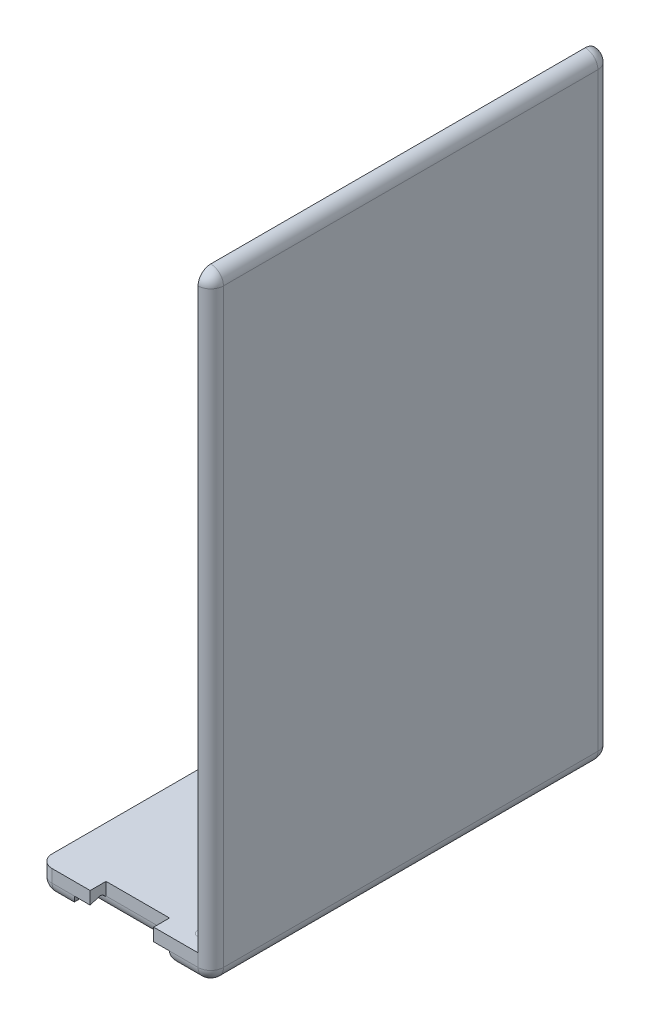
SolidWorks part; units mm, degrees
note: The reader was unsure of these and kept them because the rebuilt part matched: shared geometry of "Sketch6<3>".
ref_plane "Front Plane" through (0, 0, 0) normal (0, 0, 1) x (1, 0, 0)
ref_plane "Top Plane" through (0, 0, 0) normal (0, 1, 0) x (1, 0, 0)
ref_plane "Right Plane" through (0, 0, 0) normal (1, 0, 0) x (0, 0, -1)
sketch "Sketch1" plane through (0, 0, 0) normal (0, 1, 0) x (1, 0, 0)
  line L1 (0, 0) -> (-25, 0)
  line L2 (0, 0) -> (0, -63)
  line L3 (0, -63) -> (-25, -63)
  line L4 (-25, 0) -> (-25, -63)
  dimension "D1" = 63
  dimension "D2" = 25
extrude "Boss-Extrude1" add sketch "Sketch1" along normal blind 4
sketch "Sketch3" plane through (0, 0, 0) normal (1, 0, 0) x (0, 0, -1)
  line L1 (-63, 0) -> (0, 0)
  line L2 (-63, 0) -> (-63, 4)
  line L3 (-63, 4) -> (0, 4)
  line L4 (0, 0) -> (0, 4)
extrude "Boss-Extrude2" add sketch "Sketch3" along normal blind 2
sketch "Sketch4" plane through (0, 4, 0) normal (0, 1, 0) x (1, 0, 0)
  line L1 (2, -63) -> (0, -63)
  line L2 (2, -63) -> (2, 0)
  line L3 (2, 0) -> (0, 0)
  line L4 (0, -63) -> (0, 0)
extrude "Boss-Extrude3" add sketch "Sketch4" along normal blind 93
sketch "Sketch6" plane through (0, 0, 0) normal (0, -1, 0) x (1, 0, 0)
  line L0 (-25, 63) -> (2, 63) construction
  line L1 (-7, 63) -> (-17, 63)
  line L2 (-7, 63) -> (-7, 60.5)
  line L3 (-7, 60.5) -> (-17, 60.5)
  line L4 (-17, 63) -> (-17, 60.5)
  line L5 (2, 0) -> (-25, 0) construction
  line L6 (-7, 0) -> (-17, 0)
  line L7 (-7, 0) -> (-7, 2.5)
  line L8 (-7, 2.5) -> (-17, 2.5)
  line L9 (-17, 0) -> (-17, 2.5)
  line L10 (-25, 0) -> (-25, 63) construction
  dimension "D1" = 2.5
  dimension "D2" = 2.5
  dimension "D3" = 10
  dimension "D4" = 10
  dimension "D5" = 8
  dimension "D6" = 8
extrude "Cut-Extrude1" cut sketch "Sketch6" against normal through all contours L8 L9 L6 L7
extrude "Cut-Extrude2" cut sketch "Sketch6<3>" against normal blind 80 contours L3 L4 L1 L2
sketch "Sketch6<3>" plane through (0, 0, 0) normal (0, -1, 0) x (1, 0, 0) same geometry as "Sketch6"
sketch "Sketch8" plane through (0, 0, 63) normal (0, 0, 1) x (1, 0, 0)
  line L0 (-7, 0) -> (2, 0) construction
  line L1 (-4.5, 0) -> (-19.5, 0)
  line L2 (-4.5, 0) -> (-4.5, 2)
  line L3 (-4.5, 2) -> (-19.5, 2)
  line L4 (-19.5, 0) -> (-19.5, 2)
  line L5 (-25, 4) -> (-25, 0) construction
  dimension "D1" = 2
  dimension "D2" = 15
  dimension "D3" = 5.5
extrude "Cut-Extrude3" cut sketch "Sketch8" against normal blind 2.5
sketch "Sketch9" plane through (-4.5, 0, 0) normal (-1, 0, 0) x (0, 0, 1)
  line L0 (63, 0) -> (63, 2) construction
  line L1 (60.5, 2) -> (63, 2) construction
  line L2 (61.5, 2.5) -> (63, 2)
  line L3 (63, 2) -> (61.5, 2)
  line L4 (61.5, 2) -> (61.5, 2.5)
  circle A0 centre (61.5, 1.5) radius 1
  line M3 (63, 2) -> (60.5, 2)
  dimension "D1" = 2
  dimension "D2" = 1.5
  dimension "D3" = 0.5
extrude "Cut-Extrude5" cut sketch "Sketch9" along a picked direction on the side of the normal blind 15 contours A0 L3 M3 | L4 A0 M3
sketch "Sketch10" plane through (0, 0, 0) normal (0, -1, 0) x (1, 0, 0)
  line L0 (2, 31.5) -> (-25, 31.5) construction
  line L1 (2, 63) -> (2, 0) construction
  line L2 (-25, 0) -> (-25, 63) construction
  line L3 (-25, 31.5) -> (2, 31.5) construction
sketch "Sketch11" plane through (0, 0, 0) normal (0, 0, -1) x (-1, 0, 0)
  line L0 (-2, 0) -> (7, 0) construction
  line L1 (4.5, 0) -> (19.5, 0)
  line L2 (4.5, 0) -> (4.5, 2)
  line L3 (4.5, 2) -> (19.5, 2)
  line L4 (19.5, 0) -> (19.5, 2)
  line L5 (25, 4) -> (25, 0) construction
  dimension "D1" = 2
  dimension "D2" = 15
  dimension "D3" = 5.5
extrude "Cut-Extrude6" cut sketch "Sketch11" against normal blind 3 contours L2 L3 L4 L1
sketch "Sketch12" plane through (-4.5, 0, 0) normal (-1, 0, 0) x (0, 0, 1)
  line L0 (0, 0) -> (0, 2) construction
  line L1 (3, 2) -> (0, 2) construction
  line L2 (1.9, 2.5) -> (0, 2)
  line L3 (0, 2) -> (1.9, 2)
  line L4 (1.9, 2) -> (1.9, 2.5)
  circle A0 centre (1.9, 1.5) radius 1
  line M4 (3, 2) -> (0, 2)
  dimension "D1" = 2
  dimension "D2" = 1.9
  dimension "D3" = 0.5
extrude "Cut-Extrude7" cut sketch "Sketch12" along normal blind 15 contours A0 M4 | A0 L4 M4
fillet "Fillet6" radius 2 20 edges at (-22.25, 0, 0) (-12, 0, 3) (-19.5, 0, 1.5) (-4.5, 1, 0) (-4.5, 0, 1.5) (-19.5, 1, 3) (-4.5, 1, 3) (-19.5, 1, 0) (2, 0, 31.5) (-22.25, 0, 63) (-25, 0, 31.5) (-1.25, 0, 0) (-12, 0, 60.5) (-1.25, 0, 63) (-19.5, 1, 63) (-4.5, 1, 60.5) (-4.5, 0, 61.75) (-19.5, 1, 60.5) (-19.5, 0, 61.75) (-4.5, 1, 63)
fillet "Fillet7" radius 2 4 edges at (-24.4142, 0.5858, 62.4142) (-24.4142, 0.5858, 0.5858) (-25, 3, 63) (-25, 3, 0)
sketch "Sketch13" plane through (0, 4, 0) normal (0, 1, 0) x (1, 0, 0)
  line L6 (0, -4.25) -> (-1.5, -4.25)
  line L7 (0, 0) -> (0, -63) construction
  line L8 (-1.5, -4.25) -> (-1.5, -2.6)
  line L9 (-1.5, -2.6) -> (-2.7, -2.6)
  line L10 (-2.7, -2.6) -> (-2.7, -5.6)
  line L11 (-2.7, -5.6) -> (0, -5.6)
  line L12 (0, 0) -> (-7, 0) construction
  line L13 (0, -4.25) -> (0, -5.6)
  line L14 (0, -31.5) -> (-25.0562, -31.5) construction
  line L15 (-1.5, -60.4) -> (-2.7, -60.4)
  line L16 (-2.7, -60.4) -> (-2.7, -57.4)
  line L17 (-2.7, -57.4) -> (0, -57.4)
  line L18 (0, -58.75) -> (0, -57.4)
  line L19 (0, -58.75) -> (-1.5, -58.75)
  line L20 (-1.5, -58.75) -> (-1.5, -60.4)
  dimension "D1" = 1.5
  dimension "D2" = 1.2
  dimension "D3" = 2.6
  dimension "D4" = 3
  dimension "D5" = 1.35
extrude "Boss-Extrude4" add sketch "Sketch13" along normal blind 79
fillet "Fillet8" radius 0.4 24 edges at (-1.5, 4, 3.425) (0, 83, 4.925) (0, 83, 58.075) (-1.5, 4, 59.575) (-1.5, 43.5, 2.6) (-2.1, 83, 2.6) (-2.1, 4, 2.6) (-2.7, 43.5, 2.6) (-2.7, 83, 4.1) (-2.7, 4, 4.1) (-2.7, 43.5, 5.6) (-1.35, 83, 5.6) (0, 43.5, 5.6) (-1.35, 4, 5.6) (0, 43.5, 57.4) (-1.35, 83, 57.4) (-1.35, 4, 57.4) (-2.7, 43.5, 57.4) (-2.7, 83, 58.9) (-2.7, 4, 58.9) (-2.7, 43.5, 60.4) (-2.1, 83, 60.4) (-1.5, 43.5, 60.4) (-2.1, 4, 60.4)
fillet "Fillet9" radius 2 7 edges at (2, 49.5, 63) (2, 49.5, 0) (1.4142, 0.5858, 62.4142) (1.4142, 0.5858, 0.5858) (2, 97, 31.5) (1, 97, 0) (1, 97, 63)
sketch "Sketch14" plane through (0, 0, 0) normal (0, -1, 0) x (-1, 0, 0)
  line L0 (12, -58.5) -> (12, -5) construction
  line L1 (2.5, -58.5) -> (21.5, -58.5) construction
  line L2 (21.5, -5) -> (2.5, -5) construction
  text T0 "EMG\r\n" font "Century Gothic" height in points 36
extrude "Cut-Extrude8" cut sketch "Sketch14" against normal blind 2
